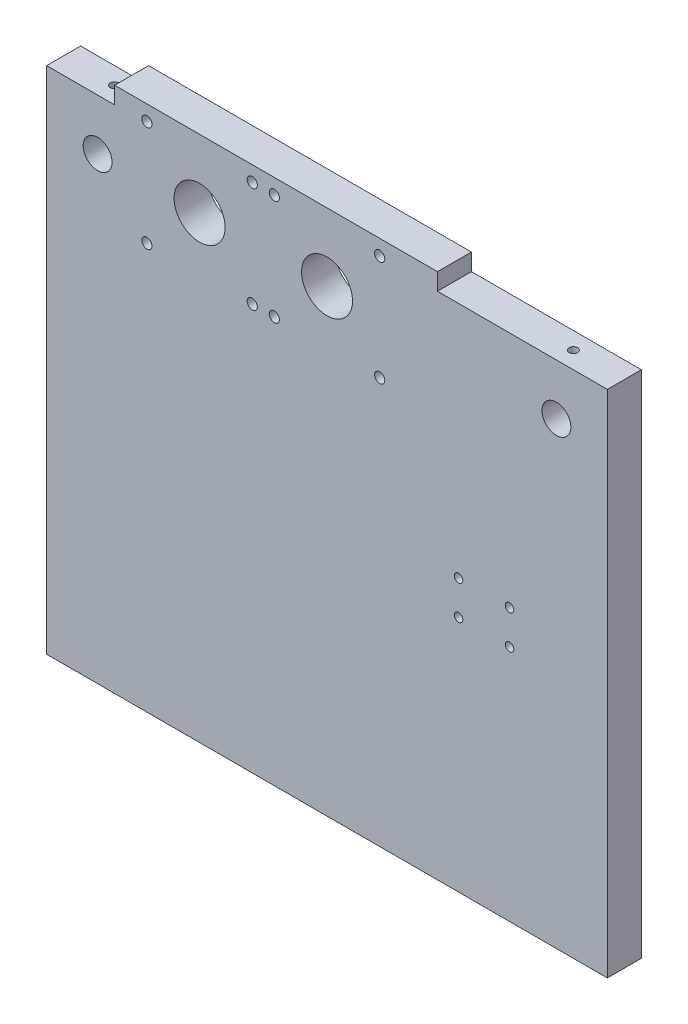
SolidWorks part; units mm, degrees
ref_plane "Plan de face" through (0, 0, 0) normal (0, 0, 1) x (1, 0, 0)
ref_plane "Plan de dessus" through (0, 0, 0) normal (0, 1, 0) x (1, 0, 0)
ref_plane "Plan de droite" through (0, 0, 0) normal (1, 0, 0) x (0, 0, -1)
sketch "Esquisse1" plane through (0, 0, 0) normal (0, 0, 1) x (1, 0, 0)
  line L1 (-82.5, -75) -> (82.5, -75)
  line L2 (-82.5, -75) -> (-82.5, 75)
  line L3 (-82.5, 75) -> (82.5, 75)
  line L4 (82.5, -75) -> (82.5, 75)
  line L5 (-82.5, -75) -> (82.5, 75) construction
  line L6 (-82.5, 75) -> (82.5, -75) construction
  point P0 (0, 0)
  dimension "D1" = 150
  dimension "D2" = 165
extrude "Boss.-Extru.1" add sketch "Esquisse1" along normal blind 10
sketch "Esquisse2" plane through (0, 0, 10) normal (0, 0, 1) x (1, 0, 0)
  line L0 (-82.5, 75) -> (-82.5, -75) construction
  line L2 (82.5, 75) -> (-82.5, 75) construction
  line L3 (0, 14.3557) -> (0, 51.8048) construction
  circle A0 centre (-67.5, 60) radius 4.25
  circle A1 centre (67.5, 60) radius 4.25
  dimension "D1" = 8.5
  dimension "D2" = 15
  dimension "D3" = 15
extrude "Enlèv. mat.-Extru.1" cut sketch "Esquisse2" against normal blind 10
sketch "Esquisse4" plane through (0, 0, 10) normal (0, 0, 1) x (1, 0, 0)
  line L0 (-15.5, 75.5) -> (0.6525, 75.5) construction
  line L1 (0.6525, 75.5) -> (0.6525, 68.0179) construction
  line L2 (-15.5, 75.5) -> (15.5, 44.5) construction
  line L3 (-67.5, 60) -> (67.1307, 60) construction
  line L5 (-53, 75.5) -> (-27.6278, 75.5) construction
  line L6 (-27.6278, 75.5) -> (-27.6278, 68.0179) construction
  line L7 (-53, 75.5) -> (-22, 44.5) construction
  circle A0 centre (-15.5, 75.5) radius 1.5
  circle A1 centre (15.5, 75.5) radius 1.5
  circle A2 centre (15.5, 44.5) radius 1.5
  circle A3 centre (-15.5, 44.5) radius 1.5
  circle A4 centre (0, 60) radius 7.5
  circle A5 centre (-53, 75.5) radius 1.5
  circle A6 centre (-22, 75.5) radius 1.5
  circle A7 centre (-22, 44.5) radius 1.5
  circle A8 centre (-53, 44.5) radius 1.5
  circle A9 centre (-37.5, 60) radius 7.5
  dimension "D1" = 3
  dimension "D4" = 15
  dimension "D5" = 31
  dimension "D6" = 31
  dimension "D7" = 15
  dimension "D9" = 31
  dimension "D10" = 37.5
  dimension "D8" = 31
  dimension "D2" = 2
  dimension "D3" = 2
sketch "Esquisse5" plane through (0, 75, 0) normal (0, 1, 0) x (1, 0, 0)
  line L0 (-67.5, -10) -> (67.1307, -10) construction
  line L1 (-62.5, -10) -> (32.5, -10)
  line L2 (-62.5, -10) -> (-62.5, 0)
  line L3 (-62.5, 0) -> (32.5, 0)
  line L4 (32.5, -10) -> (32.5, 0)
  line L5 (82.5, 0) -> (-82.5, 0) construction
  line L6 (-82.5, -10) -> (-82.5, 0) construction
  line L7 (82.5, -10) -> (82.5, 0) construction
  dimension "D1" = 20
  dimension "D2" = 50
extrude "Boss.-Extru.2" add sketch "Esquisse5" along normal blind 5
extrude "Enlèv. mat.-Extru.2" cut sketch "Esquisse4" against normal blind 15
sketch "Esquisse6" plane through (0, 0, 10) normal (0, 0, 1) x (1, 0, 0)
  line L0 (38.7151, 5) -> (53.7151, 5) construction
  line L1 (53.7151, 5) -> (53.7151, -5) construction
  line L2 (53.7151, -5) -> (38.7151, -5) construction
  line L3 (38.7151, -5) -> (38.7151, 5) construction
  line L4 (7.5, 60) -> (63.25, 60) construction
  line L5 (0, 0) -> (82.5, 0) construction
  line L6 (82.5, -75) -> (82.5, 75) construction
  circle A0 centre (38.7151, 5) radius 1.25
  circle A1 centre (53.7151, 5) radius 1.25
  circle A2 centre (53.7151, -5) radius 1.25
  circle A3 centre (38.7151, -5) radius 1.25
  circle A4 centre (0, 60) radius 7.5 construction
  circle A5 centre (67.5, 60) radius 4.25 construction
  dimension "D1" = 2.5
  dimension "D5" = 2.5
  dimension "D6" = 2.5
  dimension "D7" = 2.5
  dimension "D2" = 15
  dimension "D3" = 10
  dimension "D4" = 10
  dimension "D8" = 5
extrude "Enlèv. mat.-Extru.3" cut sketch "Esquisse6" against normal blind 10 contours A0 | A3 | A2 | A1 region at (38.7151, 5, 10) region at (53.7151, -5, 10) region at (38.7151, -5, 10)
sketch "Esquisse7" plane through (0, 0, 0) normal (0, 0, -1) x (-1, 0, 0)
  line L1 (-15, -10) -> (15, -10)
  line L2 (-15, -10) -> (-15, 10)
  line L3 (-15, 10) -> (15, 10)
  line L4 (15, -10) -> (15, 10)
  line L5 (-15, -10) -> (15, 10) construction
  line L6 (-15, 10) -> (15, -10) construction
  point P0 (0, 0)
  dimension "D1" = 30
  dimension "D2" = 20
extrude "Boss.-Extru.3" add sketch "Esquisse7" along normal blind 30
sketch "Esquisse8" plane through (0, 10, 0) normal (0, 1, 0) x (1, 0, 0)
  line L0 (32.5, 0) -> (-62.5, 0) construction
  circle A0 centre (0, 15) radius 11.5
  circle A1 centre (0, 15) radius 5.5
  circle A2 centre (0, 23) radius 2
  circle A3 centre (8, 15) radius 2
  circle A4 centre (0, 7) radius 2
  circle A5 centre (-8, 15) radius 2
  point P16 (0, 15)
  dimension "D1" = 23
  dimension "D2" = 11
  dimension "D4" = 4
  dimension "D5" = 8
  dimension "D3" = 15
  dimension "D6" = 4
extrude "Enlèv. mat.-Extru.4" cut sketch "Esquisse8" against normal blind 30 contours A1 | A5 | A2 | A3 | A4 region at (0, 10, -15)
extrude "Enlèv. mat.-Extru.5" cut sketch "Esquisse8<4>" against normal blind 5
sketch "Esquisse8<4>" plane through (0, 10, 0) normal (0, 1, 0) x (1, 0, 0) same geometry as "Esquisse8"
sketch "Esquisse9" plane through (0, 75, 0) normal (0, 1, 0) x (1, 0, 0)
  line L0 (82.5, -5) -> (56.7618, -5) construction
  line L1 (82.5, -10) -> (82.5, 0) construction
  line L3 (0, -22) -> (0, 22) construction
  circle A0 centre (67.5, -5) radius 1.25
  circle A1 centre (-67.5, -5) radius 1.25
  dimension "D1" = 2.5
  dimension "D2" = 15
extrude "Enlèv. mat.-Extru.6" cut sketch "Esquisse9" against normal blind 15
